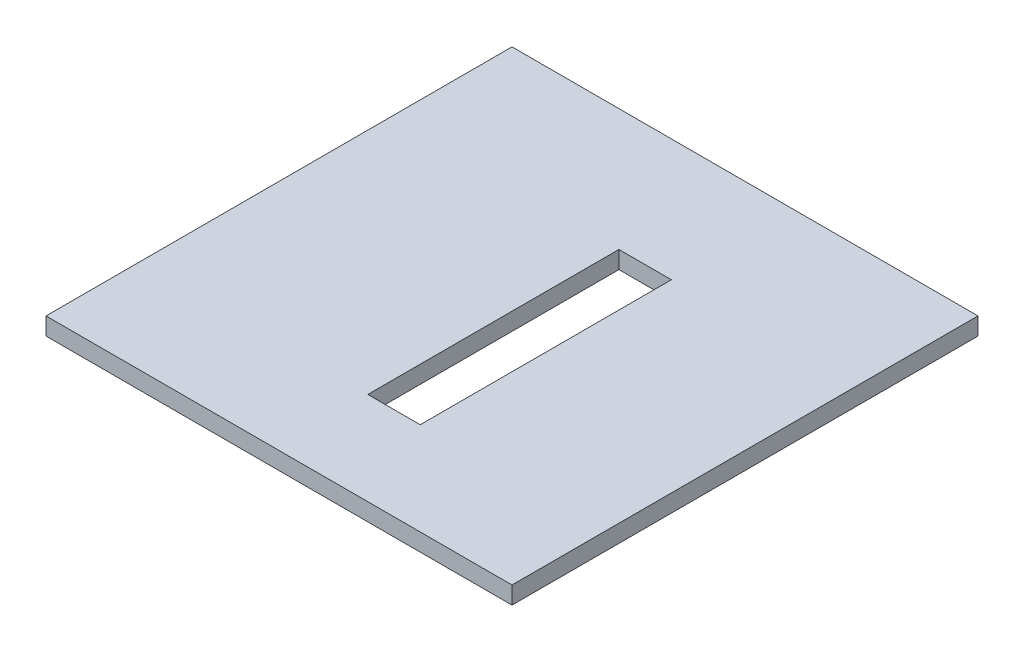
SolidWorks part; units mm, degrees
ref_plane "Front Plane" through (0, 0, 0) normal (0, 0, 1) x (1, 0, 0)
ref_plane "Top Plane" through (0, 0, 0) normal (0, 1, 0) x (1, 0, 0)
ref_plane "Right Plane" through (0, 0, 0) normal (1, 0, 0) x (0, 0, -1)
sketch "Sketch1" plane through (0, 0, 0) normal (0, 1, 0) x (1, 0, 0)
  line L0 (80, 0) -> (80, 80) construction
  line L1 (0, 0) -> (80, 0)
  line L2 (0, 0) -> (0, 80)
  line L3 (0, 80) -> (80, 80)
  line L4 (80, 0) -> (80, 80)
  line L5 (80, 80) -> (0, 80) construction
  line L7 (39.3, 15.9432) -> (48.3, 15.9432)
  line L8 (39.3, 15.9432) -> (39.3, 59.0568)
  line L9 (39.3, 59.0568) -> (48.3, 59.0568)
  line L10 (48.3, 15.9432) -> (48.3, 59.0568)
  line L12 (45.3, 15.9432) -> (45.3, 59.0568) construction
  line L13 (42.3, 59.0568) -> (42.3, 15.9432) construction
  line L14 (45.3, 16.5) -> (45.3, 58.5) construction
  line L15 (42.3, 16.5) -> (42.3, 58.5) construction
  line L17 (45.3, 37.5) -> (48.3, 37.5) construction
  line L18 (42.3, 40) -> (39.3, 40) construction
  line L20 (42.3, 37.5) -> (39.3, 37.5) construction
sketch "Sketch2" plane through (0, 0, 0) normal (0, 0, 1) x (1, 0, 0)
  line L1 (0, 0) -> (80, 0)
  line L2 (0, 0) -> (0, -3)
  line L3 (0, -3) -> (80, -3)
  line L4 (80, 0) -> (80, -3)
extrude "Boss-Extrude1" add sketch "Sketch1" against normal up to vertex (3 mm away) up to point (0, -3, 0)
